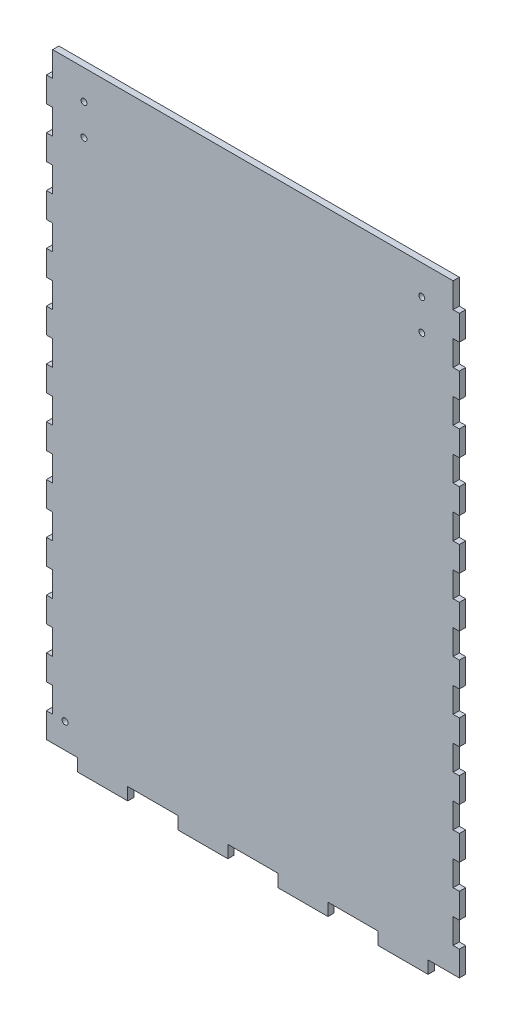
SolidWorks part; units mm, degrees
material "Acrylic (Medium-high impact)"
ref_plane "Front Plane" through (0, 0, 0) normal (0, 0, 1) x (1, 0, 0)
ref_plane "Top Plane" through (0, 0, 0) normal (0, 1, 0) x (1, 0, 0)
ref_plane "Right Plane" through (0, 0, 0) normal (1, 0, 0) x (0, 0, -1)
sketch "Sketch1" plane through (0, 0, 0) normal (0, 0, 1) x (1, 0, 0)
  line L0 (0, 0) -> (203.2, 0)
  line L1 (203.2, 0) -> (203.2, 304.8)
  line L2 (203.2, 304.8) -> (0, 304.8)
  line L3 (0, 304.8) -> (0, 0)
  dimension "D1" = 203.2
  dimension "D2" = 304.8
extrude "Boss-Extrude1" add sketch "Sketch1" along normal blind 3.175
sketch "Sketch2" plane through (0, 0, 3.175) normal (0, 0, 1) x (1, 0, 0)
  line L0 (0, 304.8) -> (-3.175, 304.8)
  line L1 (-3.175, 304.8) -> (-3.175, 292.1)
  line L2 (-3.175, 292.1) -> (0, 292.1)
  line L3 (0, 304.8) -> (0, 0) construction
  line L4 (0, 292.1) -> (0, 304.8)
  line L5 (101.6, 304.8) -> (101.6, 0) construction
  line L6 (203.2, 304.8) -> (0, 304.8) construction
  line L7 (0, 0) -> (203.2, 0) construction
  line L8 (206.375, 292.1) -> (203.2, 292.1)
  line L9 (206.375, 304.8) -> (206.375, 292.1)
  line L10 (203.2, 304.8) -> (206.375, 304.8)
  line L11 (203.2, 292.1) -> (203.2, 304.8)
  line L12 (0, 266.7) -> (0, 279.4)
  line L13 (0, 279.4) -> (-3.175, 279.4)
  line L14 (-3.175, 279.4) -> (-3.175, 266.7)
  line L15 (-3.175, 266.7) -> (0, 266.7)
  line L16 (206.375, 266.7) -> (203.2, 266.7)
  line L17 (203.2, 266.7) -> (203.2, 279.4)
  line L18 (203.2, 279.4) -> (206.375, 279.4)
  line L19 (206.375, 279.4) -> (206.375, 266.7)
  line L20 (0, 241.3) -> (0, 254)
  line L21 (0, 254) -> (-3.175, 254)
  line L22 (-3.175, 254) -> (-3.175, 241.3)
  line L23 (-3.175, 241.3) -> (0, 241.3)
  line L24 (206.375, 241.3) -> (203.2, 241.3)
  line L25 (203.2, 241.3) -> (203.2, 254)
  line L26 (203.2, 254) -> (206.375, 254)
  line L27 (206.375, 254) -> (206.375, 241.3)
  line L28 (0, 215.9) -> (0, 228.6)
  line L29 (0, 228.6) -> (-3.175, 228.6)
  line L30 (-3.175, 228.6) -> (-3.175, 215.9)
  line L31 (-3.175, 215.9) -> (0, 215.9)
  line L32 (206.375, 215.9) -> (203.2, 215.9)
  line L33 (203.2, 215.9) -> (203.2, 228.6)
  line L34 (203.2, 228.6) -> (206.375, 228.6)
  line L35 (206.375, 228.6) -> (206.375, 215.9)
  line L36 (0, 190.5) -> (0, 203.2)
  line L37 (0, 203.2) -> (-3.175, 203.2)
  line L38 (-3.175, 203.2) -> (-3.175, 190.5)
  line L39 (-3.175, 190.5) -> (0, 190.5)
  line L40 (206.375, 190.5) -> (203.2, 190.5)
  line L41 (203.2, 190.5) -> (203.2, 203.2)
  line L42 (203.2, 203.2) -> (206.375, 203.2)
  line L43 (206.375, 203.2) -> (206.375, 190.5)
  line L44 (0, 165.1) -> (0, 177.8)
  line L45 (0, 177.8) -> (-3.175, 177.8)
  line L46 (-3.175, 177.8) -> (-3.175, 165.1)
  line L47 (-3.175, 165.1) -> (0, 165.1)
  line L48 (206.375, 165.1) -> (203.2, 165.1)
  line L49 (203.2, 165.1) -> (203.2, 177.8)
  line L50 (203.2, 177.8) -> (206.375, 177.8)
  line L51 (206.375, 177.8) -> (206.375, 165.1)
  line L52 (0, 139.7) -> (0, 152.4)
  line L53 (0, 152.4) -> (-3.175, 152.4)
  line L54 (-3.175, 152.4) -> (-3.175, 139.7)
  line L55 (-3.175, 139.7) -> (0, 139.7)
  line L56 (206.375, 139.7) -> (203.2, 139.7)
  line L57 (203.2, 139.7) -> (203.2, 152.4)
  line L58 (203.2, 152.4) -> (206.375, 152.4)
  line L59 (206.375, 152.4) -> (206.375, 139.7)
  line L60 (0, 114.3) -> (0, 127)
  line L61 (0, 127) -> (-3.175, 127)
  line L62 (-3.175, 127) -> (-3.175, 114.3)
  line L63 (-3.175, 114.3) -> (0, 114.3)
  line L64 (206.375, 114.3) -> (203.2, 114.3)
  line L65 (203.2, 114.3) -> (203.2, 127)
  line L66 (203.2, 127) -> (206.375, 127)
  line L67 (206.375, 127) -> (206.375, 114.3)
  line L68 (0, 88.9) -> (0, 101.6)
  line L69 (0, 101.6) -> (-3.175, 101.6)
  line L70 (-3.175, 101.6) -> (-3.175, 88.9)
  line L71 (-3.175, 88.9) -> (0, 88.9)
  line L72 (206.375, 88.9) -> (203.2, 88.9)
  line L73 (203.2, 88.9) -> (203.2, 101.6)
  line L74 (203.2, 101.6) -> (206.375, 101.6)
  line L75 (206.375, 101.6) -> (206.375, 88.9)
  line L76 (0, 63.5) -> (0, 76.2)
  line L77 (0, 76.2) -> (-3.175, 76.2)
  line L78 (-3.175, 76.2) -> (-3.175, 63.5)
  line L79 (-3.175, 63.5) -> (0, 63.5)
  line L80 (206.375, 63.5) -> (203.2, 63.5)
  line L81 (203.2, 63.5) -> (203.2, 76.2)
  line L82 (203.2, 76.2) -> (206.375, 76.2)
  line L83 (206.375, 76.2) -> (206.375, 63.5)
  line L84 (0, 38.1) -> (0, 50.8)
  line L85 (0, 50.8) -> (-3.175, 50.8)
  line L86 (-3.175, 50.8) -> (-3.175, 38.1)
  line L87 (-3.175, 38.1) -> (0, 38.1)
  line L88 (206.375, 38.1) -> (203.2, 38.1)
  line L89 (203.2, 38.1) -> (203.2, 50.8)
  line L90 (203.2, 50.8) -> (206.375, 50.8)
  line L91 (206.375, 50.8) -> (206.375, 38.1)
  line L92 (0, 12.7) -> (0, 25.4)
  line L93 (0, 25.4) -> (-3.175, 25.4)
  line L94 (-3.175, 25.4) -> (-3.175, 12.7)
  line L95 (-3.175, 12.7) -> (0, 12.7)
  line L96 (206.375, 12.7) -> (203.2, 12.7)
  line L97 (203.2, 12.7) -> (203.2, 25.4)
  line L98 (203.2, 25.4) -> (206.375, 25.4)
  line L99 (206.375, 25.4) -> (206.375, 12.7)
  line L100 (0, 292.1) -> (0, 266.7) construction
  line L101 (12.7, 0) -> (12.7, -6.35)
  line L102 (12.7, -6.35) -> (38.1, -6.35)
  line L103 (38.1, -6.35) -> (38.1, 0)
  line L104 (38.1, 0) -> (12.7, 0)
  line L105 (88.9, 0) -> (63.5, 0)
  line L106 (63.5, 0) -> (63.5, -6.35)
  line L107 (63.5, -6.35) -> (88.9, -6.35)
  line L108 (88.9, -6.35) -> (88.9, 0)
  line L109 (139.7, 0) -> (114.3, 0)
  line L110 (114.3, 0) -> (114.3, -6.35)
  line L111 (114.3, -6.35) -> (139.7, -6.35)
  line L112 (139.7, -6.35) -> (139.7, 0)
  line L113 (190.5, 0) -> (165.1, 0)
  line L114 (165.1, 0) -> (165.1, -6.35)
  line L115 (165.1, -6.35) -> (190.5, -6.35)
  line L116 (190.5, -6.35) -> (190.5, 0)
  line L117 (38.1, 0) -> (88.9, 0) construction
  dimension "D1" = 3.175
  dimension "D2" = 12.7
  dimension "D4" = 25.4
  dimension "D5" = 12.7
  dimension "D6" = 6.35
  dimension "D7" = 25.4
  dimension "D9" = 50.8
  dimension "D3" = 12
  dimension "D8" = 4
extrude "Boss-Extrude2" [suppressed] add sketch "Sketch2" against normal up to surface (3.175 mm away) up to face at (101.6, 152.4, 0)
sketch "Sketch3" plane through (0, 0, 3.175) normal (0, 0, 1) x (1, 0, 0)
  line L0 (0, 0) -> (-3.175, 0)
  line L1 (-3.175, 0) -> (-3.175, 12.7)
  line L2 (-3.175, 12.7) -> (0, 12.7)
  line L3 (0, 304.8) -> (0, 0) construction
  line L4 (0, 12.7) -> (0, 0)
  line L5 (101.6, 304.8) -> (101.6, 0) construction
  line L6 (203.2, 304.8) -> (0, 304.8) construction
  line L7 (0, 0) -> (203.2, 0) construction
  line L8 (206.375, 12.7) -> (203.2, 12.7)
  line L9 (206.375, 0) -> (206.375, 12.7)
  line L10 (203.2, 0) -> (206.375, 0)
  line L11 (203.2, 12.7) -> (203.2, 0)
  line L12 (0, 38.1) -> (0, 25.4)
  line L13 (0, 25.4) -> (-3.175, 25.4)
  line L14 (-3.175, 25.4) -> (-3.175, 38.1)
  line L15 (-3.175, 38.1) -> (0, 38.1)
  line L16 (206.375, 38.1) -> (203.2, 38.1)
  line L17 (203.2, 38.1) -> (203.2, 25.4)
  line L18 (203.2, 25.4) -> (206.375, 25.4)
  line L19 (206.375, 25.4) -> (206.375, 38.1)
  line L20 (0, 63.5) -> (0, 50.8)
  line L21 (0, 50.8) -> (-3.175, 50.8)
  line L22 (-3.175, 50.8) -> (-3.175, 63.5)
  line L23 (-3.175, 63.5) -> (0, 63.5)
  line L24 (206.375, 63.5) -> (203.2, 63.5)
  line L25 (203.2, 63.5) -> (203.2, 50.8)
  line L26 (203.2, 50.8) -> (206.375, 50.8)
  line L27 (206.375, 50.8) -> (206.375, 63.5)
  line L28 (0, 88.9) -> (0, 76.2)
  line L29 (0, 76.2) -> (-3.175, 76.2)
  line L30 (-3.175, 76.2) -> (-3.175, 88.9)
  line L31 (-3.175, 88.9) -> (0, 88.9)
  line L32 (206.375, 88.9) -> (203.2, 88.9)
  line L33 (203.2, 88.9) -> (203.2, 76.2)
  line L34 (203.2, 76.2) -> (206.375, 76.2)
  line L35 (206.375, 76.2) -> (206.375, 88.9)
  line L36 (0, 114.3) -> (0, 101.6)
  line L37 (0, 101.6) -> (-3.175, 101.6)
  line L38 (-3.175, 101.6) -> (-3.175, 114.3)
  line L39 (-3.175, 114.3) -> (0, 114.3)
  line L40 (206.375, 114.3) -> (203.2, 114.3)
  line L41 (203.2, 114.3) -> (203.2, 101.6)
  line L42 (203.2, 101.6) -> (206.375, 101.6)
  line L43 (206.375, 101.6) -> (206.375, 114.3)
  line L44 (0, 139.7) -> (0, 127)
  line L45 (0, 127) -> (-3.175, 127)
  line L46 (-3.175, 127) -> (-3.175, 139.7)
  line L47 (-3.175, 139.7) -> (0, 139.7)
  line L48 (206.375, 139.7) -> (203.2, 139.7)
  line L49 (203.2, 139.7) -> (203.2, 127)
  line L50 (203.2, 127) -> (206.375, 127)
  line L51 (206.375, 127) -> (206.375, 139.7)
  line L52 (0, 165.1) -> (0, 152.4)
  line L53 (0, 152.4) -> (-3.175, 152.4)
  line L54 (-3.175, 152.4) -> (-3.175, 165.1)
  line L55 (-3.175, 165.1) -> (0, 165.1)
  line L56 (206.375, 165.1) -> (203.2, 165.1)
  line L57 (203.2, 165.1) -> (203.2, 152.4)
  line L58 (203.2, 152.4) -> (206.375, 152.4)
  line L59 (206.375, 152.4) -> (206.375, 165.1)
  line L60 (0, 190.5) -> (0, 177.8)
  line L61 (0, 177.8) -> (-3.175, 177.8)
  line L62 (-3.175, 177.8) -> (-3.175, 190.5)
  line L63 (-3.175, 190.5) -> (0, 190.5)
  line L64 (206.375, 190.5) -> (203.2, 190.5)
  line L65 (203.2, 190.5) -> (203.2, 177.8)
  line L66 (203.2, 177.8) -> (206.375, 177.8)
  line L67 (206.375, 177.8) -> (206.375, 190.5)
  line L68 (0, 215.9) -> (0, 203.2)
  line L69 (0, 203.2) -> (-3.175, 203.2)
  line L70 (-3.175, 203.2) -> (-3.175, 215.9)
  line L71 (-3.175, 215.9) -> (0, 215.9)
  line L72 (206.375, 215.9) -> (203.2, 215.9)
  line L73 (203.2, 215.9) -> (203.2, 203.2)
  line L74 (203.2, 203.2) -> (206.375, 203.2)
  line L75 (206.375, 203.2) -> (206.375, 215.9)
  line L76 (0, 241.3) -> (0, 228.6)
  line L77 (0, 228.6) -> (-3.175, 228.6)
  line L78 (-3.175, 228.6) -> (-3.175, 241.3)
  line L79 (-3.175, 241.3) -> (0, 241.3)
  line L80 (206.375, 241.3) -> (203.2, 241.3)
  line L81 (203.2, 241.3) -> (203.2, 228.6)
  line L82 (203.2, 228.6) -> (206.375, 228.6)
  line L83 (206.375, 228.6) -> (206.375, 241.3)
  line L84 (0, 266.7) -> (0, 254)
  line L85 (0, 254) -> (-3.175, 254)
  line L86 (-3.175, 254) -> (-3.175, 266.7)
  line L87 (-3.175, 266.7) -> (0, 266.7)
  line L88 (206.375, 266.7) -> (203.2, 266.7)
  line L89 (203.2, 266.7) -> (203.2, 254)
  line L90 (203.2, 254) -> (206.375, 254)
  line L91 (206.375, 254) -> (206.375, 266.7)
  line L92 (0, 292.1) -> (0, 279.4)
  line L93 (0, 279.4) -> (-3.175, 279.4)
  line L94 (-3.175, 279.4) -> (-3.175, 292.1)
  line L95 (-3.175, 292.1) -> (0, 292.1)
  line L96 (206.375, 292.1) -> (203.2, 292.1)
  line L97 (203.2, 292.1) -> (203.2, 279.4)
  line L98 (203.2, 279.4) -> (206.375, 279.4)
  line L99 (206.375, 279.4) -> (206.375, 292.1)
  line L100 (0, 12.7) -> (0, 38.1) construction
  line L101 (12.7, 0) -> (12.7, -6.35)
  line L102 (12.7, -6.35) -> (38.1, -6.35)
  line L103 (38.1, -6.35) -> (38.1, 0)
  line L104 (38.1, 0) -> (12.7, 0)
  line L105 (88.9, 0) -> (63.5, 0)
  line L106 (63.5, 0) -> (63.5, -6.35)
  line L107 (63.5, -6.35) -> (88.9, -6.35)
  line L108 (88.9, -6.35) -> (88.9, 0)
  line L109 (139.7, 0) -> (114.3, 0)
  line L110 (114.3, 0) -> (114.3, -6.35)
  line L111 (114.3, -6.35) -> (139.7, -6.35)
  line L112 (139.7, -6.35) -> (139.7, 0)
  line L113 (190.5, 0) -> (165.1, 0)
  line L114 (165.1, 0) -> (165.1, -6.35)
  line L115 (165.1, -6.35) -> (190.5, -6.35)
  line L116 (190.5, -6.35) -> (190.5, 0)
  line L117 (38.1, 0) -> (88.9, 0) construction
  dimension "D1" = 3.175
  dimension "D2" = 12.7
  dimension "D9" = 50.8
  dimension "D3" = 12
  dimension "D8" = 4
  dimension "D4" = 25.4
  dimension "D5" = 6.35
  dimension "D6" = 25.4
  dimension "D7" = 12.7
sketch "Sketch4" [suppressed] plane through (0, 0, 3.175) normal (0, 0, 1) x (1, 0, 0)
  line L0 (50.8, 33.5) -> (50.8, 66.5) construction
  line L1 (34.3, 50) -> (67.3, 50) construction
  line L2 (0, 12.7) -> (0, 0) construction
  line L3 (88.9, 0) -> (114.3, 0) construction
  circle A0 centre (50.8, 50) radius 16.5
  circle A1 centre (25.8, 75) radius 1.5
  circle A5 centre (75.8, 75) radius 1.5
  circle A6 centre (75.8, 25) radius 1.5
  circle A7 centre (25.8, 25) radius 1.5
  dimension "D5" = 33
  dimension "D6" = 3
  dimension "D1" = 50
  dimension "D2" = 50
  dimension "D3" = 60
  dimension "D4" = 50
extrude "Cut-Extrude1" [suppressed] cut sketch "Sketch4" against normal up to surface (3.175 mm away) up to face at (101.6, 152.4, 0)
sketch "Sketch5" [suppressed] plane through (0, 0, 0) normal (0, 0, -1) x (-1, 0, 0)
  line L1 (-206.375, 304.8) -> (-206.375, 292.1) construction
  line L2 (-206.375, 304.8) -> (3.175, 304.8) construction
  line L3 (-101.6, 304.8) -> (-101.6, 0) construction
  line L4 (-88.9, 0) -> (-114.3, 0) construction
  circle A1 centre (-187.325, 289.8) radius 1.5
  circle A2 centre (-187.325, 274.05) radius 1.5
  circle A3 centre (-15.875, 274.05) radius 1.5
  circle A4 centre (-15.875, 289.8) radius 1.5
  dimension "D1" = 3
  dimension "D2" = 3
  dimension "D3" = 15.75
  dimension "D4" = 19.05
  dimension "D5" = 15
extrude "Cut-Extrude2" [suppressed] cut sketch "Sketch5" against normal up to surface (3.175 mm away) up to face at (101.6, 152.4, 3.175)
extrude "Boss-Extrude4" add sketch "Sketch3" against normal up to surface (3.175 mm away) up to face at (101.6, 152.4, 0)
sketch "Sketch6" plane through (0, 0, 0) normal (0, 0, -1) x (-1, 0, 0)
  line L1 (-203.2, 304.8) -> (0, 304.8) construction
  line L2 (-101.6, 304.8) -> (-101.6, 0) construction
  line L3 (-88.9, 0) -> (-114.3, 0) construction
  line L4 (-206.375, 292.1) -> (-206.375, 279.4) construction
  circle A0 centre (-187.325, 289.8) radius 1.5
  circle A1 centre (-187.325, 274.05) radius 1.5
  circle A2 centre (-15.875, 274.05) radius 1.5
  circle A3 centre (-15.875, 289.8) radius 1.5
  dimension "D1" = 3
  dimension "D2" = 3
  dimension "D3" = 19.05
  dimension "D4" = 15
  dimension "D5" = 15.75
extrude "Cut-Extrude3" cut sketch "Sketch6" against normal up to surface (3.175 mm away) up to face at (101.6, 130.175, 3.175)
sketch "Sketch7" [suppressed] plane through (0, 0, 3.175) normal (0, 0, 1) x (1, 0, 0)
  line L0 (159.0125, 24.45) -> (159.0125, 12.011)
  line L1 (159.0125, 12.011) -> (189.5875, 12.011)
  line L2 (189.5875, 12.011) -> (189.5875, 24.45)
  line L3 (189.5875, 24.45) -> (159.0125, 24.45)
  line L4 (206.375, 12.7) -> (206.375, 25.4) construction
  line L5 (190.5, 0) -> (203.2, 0) construction
  dimension "D1" = 16.7875
  dimension "D2" = 24.45
  dimension "D3" = 12.439
  dimension "D4" = 30.575
extrude "Cut-Extrude4" [suppressed] cut sketch "Sketch7" against normal up to surface (3.175 mm away) up to face at (17.375, 289.8, 0)
sketch "Sketch8" plane through (0, 0, 3.175) normal (0, 0, 1) x (1, 0, 0)
  line L0 (0, 25.4) -> (0, 12.7) construction
  line L1 (-3.175, 0) -> (12.7, 0) construction
  line L2 (101.6, 304.8) -> (101.6, 0) construction
  line L3 (203.2, 304.8) -> (0, 304.8) construction
  line L4 (88.9, 0) -> (114.3, 0) construction
  circle A0 centre (6.2865, 12.7) radius 1.5
  dimension "D1" = 3
  dimension "D2" = 6.2865
  dimension "D3" = 12.7
extrude "Cut-Extrude5" cut sketch "Sketch8" against normal up to surface (3.175 mm away) up to face at (17.375, 289.8, 0)
equation "\"wall_thickness\"= 0.125in"
equation "\"base_thickness\"= 0.25in"
equation "\"D1@Boss-Extrude1\"=\"wall_thickness\""
equation "\"D1@Sketch2\"=\"wall_thickness\""
equation "\"D6@Sketch2\"=\"base_thickness\""
equation "\"D1@Sketch3\"=\"wall_thickness\""
equation "\"D5@Sketch3\"=\"base_thickness\""
